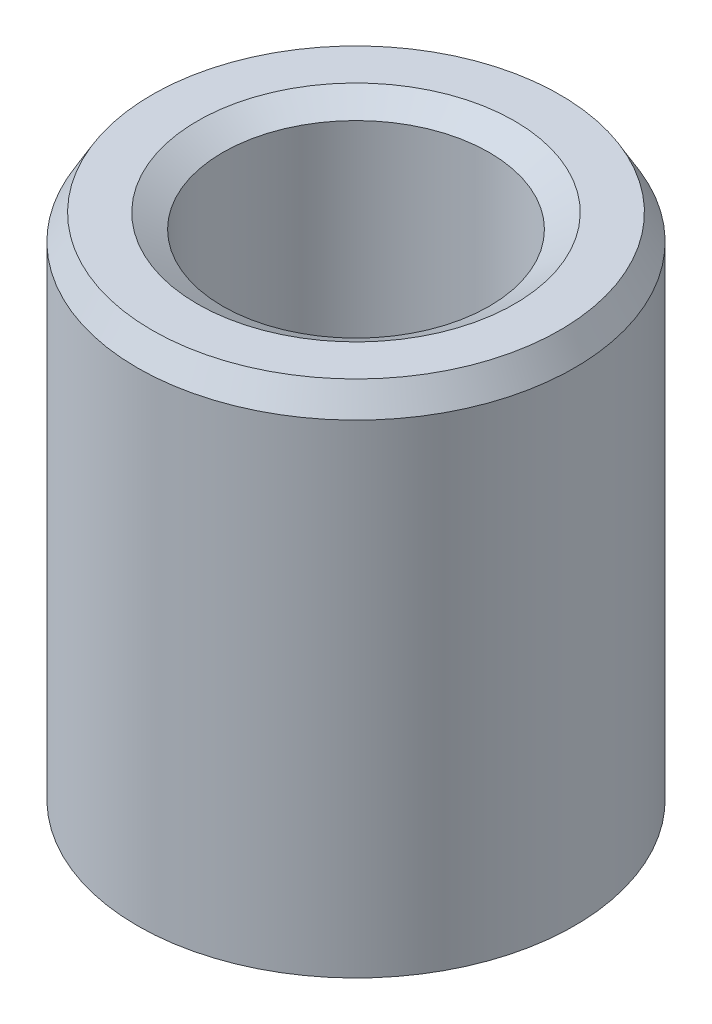
SolidWorks part; units mm, degrees
ref_plane "Front Plane" through (0, 0, 0) normal (0, 0, 1) x (1, 0, 0)
ref_plane "Top Plane" through (0, 0, 0) normal (0, 1, 0) x (1, 0, 0)
ref_plane "Right Plane" through (0, 0, 0) normal (1, 0, 0) x (0, 0, -1)
sketch "Sketch1" plane through (0, 0, 0) normal (0, 1, 0) x (1, 0, 0)
  circle A0 centre (0, 0) radius 15
  dimension "SLEEVE_OD" = 30
extrude "Boss-Extrude1" add sketch "Sketch1" along normal blind 35.8933
sketch "Sketch2" plane through (0, 0, 0) normal (0, 1, 0) x (1, 0, 0)
  circle A0 centre (0, 0) radius 9.1444
  dimension "BORE_D" = 18.2887
extrude "Cut-Extrude1" cut sketch "Sketch2" along normal through all
chamfer "Chamfer1" distance 1.7371 angle 30 4 edges at (0, 35.8933, 9.1444) (0, 0, 9.1444) (0, 0, 15) (0, 35.8933, 15) first distance on face at (0, 35.8933, 9.1444) first distance on face at (0, 0, 9.1444) first distance on face at (0, 35.8933, 15)
